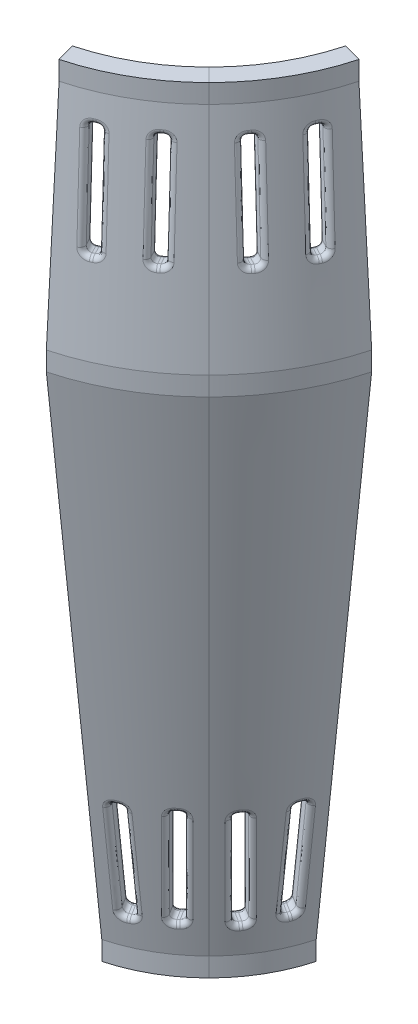
SolidWorks part; units mm, degrees
ref_plane "Front Plane" through (0, 0, 0) normal (0, 0, 1) x (1, 0, 0)
ref_plane "Top Plane" through (0, 0, 0) normal (0, 1, 0) x (1, 0, 0)
ref_plane "Right Plane" through (0, 0, 0) normal (1, 0, 0) x (0, 0, -1)
sketch "Sketch1" plane through (0, 0, 0) normal (0, 1, 0) x (1, 0, 0)
  line L0 (-28.2843, 28.2843) -> (-24.7487, 24.7487) construction
  line L1 (28.2843, 28.2843) -> (24.7487, 24.7487) construction
  line L2 (-24.7487, 24.7487) -> (0, 0) construction
  line L3 (24.7487, 24.7487) -> (0, 0) construction
  line L4 (0, 0) -> (0, 40) construction
  line L5 (-9.0587, -33.8074) -> (-10.3528, -38.637) construction
  line L6 (9.0587, -33.8074) -> (10.3528, -38.637)
  line L7 (0, 0) -> (9.0587, -33.8074) construction
  line L8 (0, 0) -> (-9.0587, -33.8074) construction
  line L9 (0, 0) -> (0, -40) construction
  line L10 (-24.7487, -24.7487) -> (-28.2843, -28.2843) construction
  line L11 (24.7487, -24.7487) -> (28.2843, -28.2843)
  line L12 (-24.7487, -24.7487) -> (0, 0) construction
  line L13 (0, 0) -> (24.7487, -24.7487) construction
  arc A0 (9.0587, -33.8074) -> (24.7487, -24.7487) centre (0, 0) ccw
  arc A1 (10.3528, -38.637) -> (28.2843, -28.2843) centre (0, 0) ccw
  arc A2 (-24.7487, -24.7487) -> (-9.0587, -33.8074) centre (0, 0) ccw construction
  arc A3 (-28.2843, -28.2843) -> (-10.3528, -38.637) centre (0, 0) ccw construction
  arc A4 (24.7487, 24.7487) -> (-24.7487, 24.7487) centre (0, 0) ccw construction
  arc A5 (28.2843, 28.2843) -> (-28.2843, 28.2843) centre (0, 0) ccw construction
  dimension "D1" = 70
  dimension "D2" = 5
  dimension "D3" = 45
  dimension "D4" = 45
  dimension "D5" = 15
  dimension "D6" = 15
  dimension "D7" = 30
  dimension "D8" = 30
ref_plane "Plane1" through (0, 152.4, 0) normal (0, 1, 0) x (1, 0, 0)
sketch "Sketch2" plane through (0, 152.4, 0) normal (0, 1, 0) x (1, 0, 0)
  line L0 (0, 0) -> (24.7487, -24.7487) construction
  line L1 (0, 0) -> (9.0587, -33.8074) construction
  line L2 (0, 0) -> (-9.0587, -33.8074) construction
  line L3 (-24.7487, -24.7487) -> (0, 0) construction
  line L4 (24.7487, 24.7487) -> (0, 0) construction
  line L5 (0, 0) -> (0, 40) construction
  line L6 (-24.7487, 24.7487) -> (0, 0) construction
  line L7 (0, 0) -> (24.7487, -24.7487) construction
  line L8 (0, 0) -> (9.0587, -33.8074) construction
  line L9 (0, 0) -> (-9.0587, -33.8074) construction
  line L10 (-24.7487, -24.7487) -> (0, 0) construction
  line L11 (24.7487, 24.7487) -> (0, 0) construction
  line L12 (0, 0) -> (0, 40) construction
  line L13 (-24.7487, 24.7487) -> (0, 0) construction
  line L14 (-42.9214, 42.9214) -> (-39.3858, 39.3858) construction
  line L15 (42.9214, 42.9214) -> (39.3858, 39.3858) construction
  line L16 (-39.3858, -39.3858) -> (-42.9214, -42.9214) construction
  line L17 (-14.4162, -53.8021) -> (-15.7103, -58.6317) construction
  line L18 (14.4162, -53.8021) -> (15.7103, -58.6317)
  line L19 (39.3858, -39.3858) -> (42.9214, -42.9214)
  arc A0 (-39.3858, -39.3858) -> (-14.4162, -53.8021) centre (0, 0) ccw construction
  arc A1 (-42.9214, -42.9214) -> (-15.7103, -58.6317) centre (0, 0) ccw construction
  arc A2 (39.3858, 39.3858) -> (-39.3858, 39.3858) centre (0, 0) ccw construction
  arc A3 (42.9214, 42.9214) -> (-42.9214, 42.9214) centre (0, 0) ccw construction
  arc A4 (14.4162, -53.8021) -> (39.3858, -39.3858) centre (0, 0) ccw
  arc A5 (15.7103, -58.6317) -> (42.9214, -42.9214) centre (0, 0) ccw
  dimension "D1" = 111.4
  dimension "D2" = 5
ref_plane "Plane2" through (0, 215.9, 0) normal (0, 1, 0) x (1, 0, 0)
sketch "Sketch3" plane through (0, 215.9, 0) normal (0, 1, 0) x (1, 0, 0)
  line L0 (-24.7487, -24.7487) -> (0, 0) construction
  line L1 (0, 0) -> (-9.0587, -33.8074) construction
  line L2 (0, 0) -> (9.0587, -33.8074) construction
  line L3 (0, 0) -> (24.7487, -24.7487) construction
  line L4 (24.7487, 24.7487) -> (0, 0) construction
  line L5 (0, 0) -> (0, 40) construction
  line L6 (-24.7487, 24.7487) -> (0, 0) construction
  line L7 (-24.7487, -24.7487) -> (0, 0) construction
  line L8 (0, 0) -> (-9.0587, -33.8074) construction
  line L9 (0, 0) -> (9.0587, -33.8074) construction
  line L10 (0, 0) -> (24.7487, -24.7487) construction
  line L11 (24.7487, 24.7487) -> (0, 0) construction
  line L12 (0, 0) -> (0, 40) construction
  line L13 (-24.7487, 24.7487) -> (0, 0) construction
  line L14 (-36.0271, 36.0271) -> (-39.5626, 39.5626) construction
  line L15 (39.5626, 39.5626) -> (36.0271, 36.0271) construction
  line L16 (-36.0271, -36.0271) -> (-39.5626, -39.5626) construction
  line L17 (-13.1868, -49.2139) -> (-14.4809, -54.0435) construction
  line L18 (13.1868, -49.2139) -> (14.4809, -54.0435)
  line L19 (36.0271, -36.0271) -> (39.5626, -39.5626)
  arc A0 (-36.0271, -36.0271) -> (-13.1868, -49.2139) centre (0, 0) ccw construction
  arc A1 (-39.5626, -39.5626) -> (-14.4809, -54.0435) centre (0, 0) ccw construction
  arc A2 (39.5626, 39.5626) -> (-39.5626, 39.5626) centre (0, 0) ccw construction
  arc A3 (36.0271, 36.0271) -> (-36.0271, 36.0271) centre (0, 0) ccw construction
  arc A4 (13.1868, -49.2139) -> (36.0271, -36.0271) centre (0, 0) ccw
  arc A5 (14.4809, -54.0435) -> (39.5626, -39.5626) centre (0, 0) ccw
  dimension "D1" = 101.9
  dimension "D2" = 5
extrude "Boss-Extrude1" add sketch "Sketch2" against normal blind 5
extrude "Boss-Extrude2" add sketch "Sketch1" along normal blind 5 separate body
loft "Loft4" add section face at (18.4306, 5, 31.9227) section face at (28.6042, 147.4, 49.544) connector at (10.3528, 5, 38.637) connector at (15.7103, 147.4, 58.6317)
extrude "Boss-Extrude3" add sketch "Sketch3" against normal blind 5 separate body
loft "Loft6" add section face at (28.6042, 152.4, 49.544) section face at (26.2697, 210.9, 45.5004) connector at (14.4162, 152.4, 53.8021) connector at (13.1868, 210.9, 49.2139)
ref_plane "Plane3" through (17.2198, -4.3931, 29.8256) normal (-0.496, 0.1265, -0.8591) x (-0.8681, -0.0476, 0.4942)
ref_plane "Plane4" through (27.85, 152.4, 48.2376) normal (-0.4984, -0.0809, -0.8632) x (-0.867, 0.0465, 0.4962)
sketch "Sketch10" plane through (27.85, 152.4, 48.2376) normal (-0.4984, -0.0809, -0.8632) x (-0.867, 0.0465, 0.4962)
  line L16 (-10.1939, 64.3626) -> (16.151, 63.1316) construction
  line L21 (16.151, 63.1316) -> (17.4255, 62.6808) construction
  line L22 (-11.5048, 64.0325) -> (-10.1939, 64.3626) construction
  line L23 (-4.9555, 51.4039) -> (-1.7839, 51.2557)
  line L24 (-4.9555, 51.4039) -> (-6.2892, 22.8601)
  line L25 (-6.2892, 22.8601) -> (-3.1176, 22.7119)
  line L26 (-1.7839, 51.2557) -> (-3.1176, 22.7119)
  line L27 (7.7411, 50.8107) -> (10.9126, 50.6625)
  line L28 (7.7411, 50.8107) -> (6.4074, 22.2668)
  line L29 (6.4074, 22.2668) -> (9.5789, 22.1186)
  line L30 (10.9126, 50.6625) -> (9.5789, 22.1186)
  line L31 (-1.7839, 51.2557) -> (7.7411, 50.8107) construction
  point P8 (2.9786, 51.0332)
  point P13 (2.9786, 63.7471)
  point P16 (11.1664, 25.8769)
  point P18 (-3.3697, 51.3298)
  dimension "D1" = 3.175
  dimension "D2" = 28.575
  dimension "D3" = 9.525
  dimension "D4" = 12.7
extrude "Cut-Extrude4" cut sketch "Sketch10" against normal through all both and the other way through all
sketch "Sketch11" plane through (17.2198, -4.3931, 29.8256) normal (-0.496, 0.1265, -0.8591) x (-0.8681, -0.0476, 0.4942)
  line L0 (-9.4971, 46.1269) -> (-7.0629, 17.6541)
  line L1 (-7.0629, 17.6541) -> (-3.8879, 17.6541)
  line L2 (-3.8879, 17.6541) -> (-6.3221, 46.1269)
  line L3 (-6.3221, 46.1269) -> (-9.4971, 46.1269)
  line L4 (1.8595, 46.2291) -> (2.1681, 17.6541)
  line L5 (2.1681, 17.6541) -> (5.3431, 17.6541)
  line L6 (5.3431, 17.6541) -> (5.0345, 46.2291)
  line L7 (5.0345, 46.2291) -> (1.8595, 46.2291)
  line L8 (-9.4918, 8.7919) -> (-21.7482, 152.1541) construction
  line L9 (8.6046, 9.6619) -> (7.051, 153.5387) construction
  ellipse E0 centre (-0.2382, 4.9541) end of major axis (-35.1978, 3.2733) minor radius 4.4287 (8.6046, 9.6619) -> (-9.4918, 8.7919) ccw construction
  dimension "D1" = 3.175
  dimension "D2" = 3.175
  dimension "D3" = 3.175
  dimension "D4" = 3.175
  dimension "D5" = 3.175
  dimension "D6" = 28.575
  dimension "D7" = 12.7
  dimension "D8" = 12.7
extrude "Cut-Extrude5" cut sketch "Sketch11" along normal through all and the other way through all
fillet "Fillet1" radius 1.27 48 edges at (31.7763, 174.8427, 43.5095) (34.2726, 175.2482, 47.8341) (30.6132, 203.3229, 41.4946) (33.1107, 203.7285, 45.8212) (13.9488, 13.0189, 33.3674) (16.4216, 12.3883, 37.6484) (17.5063, 40.6647, 41.6553) (15.0294, 41.2964, 37.367) (24.8956, 41.7358, 31.7416) (27.3711, 41.1041, 36.031) (24.4434, 12.8276, 33.0884) (21.9722, 13.4583, 28.8063) (17.74, 41.0332, 38.8815) (16.6452, 12.7594, 34.8571) (13.7, 12.6564, 36.0986) (14.7735, 40.9357, 40.086) (21.9039, 13.0475, 31.8675) (24.8416, 41.3213, 34.8275) (27.3896, 41.5257, 32.8982) (24.4732, 13.2464, 29.9749) (30.5581, 203.5376, 44.5795) (33.1382, 203.51, 42.6984) (19.5272, 203.311, 47.7259) (19.2932, 203.4958, 50.4891) (22.032, 203.7177, 52.0633) (22.2478, 203.5291, 49.2566) (20.6939, 174.8314, 49.7461) (23.4096, 175.0487, 51.2689) (23.197, 175.2378, 54.0806) (20.4636, 175.0168, 52.5162) (34.3048, 175.0305, 44.7191) (31.7177, 175.0568, 46.588)
sketch "Sketch9" plane through (17.2198, -4.3931, 29.8256) normal (-0.496, 0.1265, -0.8591) x (-0.8681, -0.0476, 0.4942)
  line L0 (-21.7482, 152.1541) -> (-8.1415, 169.3376) construction
  line L1 (-8.1415, 169.3376) -> (7.051, 153.5387) construction
  line L2 (-21.7482, 152.1541) -> (7.051, 153.5387) construction
  line L7 (-2.9281, 171.09) -> (9.7719, 171.7006)
  line L8 (-2.7841, 168.0934) -> (9.9159, 168.704)
  line L29 (9.9159, 168.704) -> (9.7719, 171.7006)
  line L31 (-13.3549, 167.5852) -> (-26.0549, 166.9746)
  line L32 (-26.0549, 166.9746) -> (-26.1989, 169.9711)
  line L33 (-26.1989, 169.9711) -> (-13.4989, 170.5817)
  line L35 (-26.1269, 168.4729) -> (9.8439, 170.2023) construction
  line L36 (-9.4918, 8.7919) -> (8.6046, 9.6619) construction
  line L38 (-7.3486, 152.8464) -> (-0.4436, 9.2269) construction
  line L40 (-11.5231, 129.4852) -> (-24.2231, 128.8746)
  line L41 (-24.2231, 128.8746) -> (-24.3671, 131.8711)
  line L42 (-24.3671, 131.8711) -> (-11.6671, 132.4817)
  line L43 (-1.0964, 132.99) -> (11.6036, 133.6006)
  line L44 (11.7477, 130.604) -> (11.6036, 133.6006)
  line L45 (-0.9523, 129.9934) -> (11.7477, 130.604)
  line L46 (-9.6913, 91.3852) -> (-22.3913, 90.7746)
  line L47 (-22.3913, 90.7746) -> (-22.5354, 93.7711)
  line L48 (-22.5354, 93.7711) -> (-9.8354, 94.3817)
  line L49 (0.7354, 94.89) -> (13.4354, 95.5006)
  line L50 (13.5795, 92.504) -> (13.4354, 95.5006)
  line L51 (0.8795, 91.8934) -> (13.5795, 92.504)
  line L52 (-7.8595, 53.2852) -> (-20.5595, 52.6746)
  line L53 (-20.5595, 52.6746) -> (-20.7036, 55.6711)
  line L54 (-20.7036, 55.6711) -> (-8.0036, 56.2817)
  line L55 (2.5672, 56.79) -> (15.2672, 57.4006)
  line L56 (15.4113, 54.404) -> (15.2672, 57.4006)
  line L57 (2.7113, 53.7934) -> (15.4113, 54.404)
  line L58 (-23.7555, 219.5043) -> (2.5877, 220.7709) construction
  arc A10 (-13.3549, 167.5852) -> (-2.7841, 168.0934) centre (-8.1415, 169.3376) ccw
  arc A11 (-2.9281, 171.09) -> (-13.4989, 170.5817) centre (-8.1415, 169.3376) ccw
  arc A12 (-1.0964, 132.99) -> (-11.6671, 132.4817) centre (-6.3097, 131.2376) ccw
  arc A13 (-11.5231, 129.4852) -> (-0.9523, 129.9934) centre (-6.3097, 131.2376) ccw
  arc A14 (0.7354, 94.89) -> (-9.8354, 94.3817) centre (-4.4779, 93.1376) ccw
  arc A15 (-9.6913, 91.3852) -> (0.8795, 91.8934) centre (-4.4779, 93.1376) ccw
  arc A16 (2.5672, 56.79) -> (-8.0036, 56.2817) centre (-2.6461, 55.0376) ccw
  arc A17 (-7.8595, 53.2852) -> (2.7113, 53.7934) centre (-2.6461, 55.0376) ccw
  point P46 (0, 0)
  point P47 (0, 0)
  point P48 (-10.5839, 220.1376)
  dimension "D1" = 11
  dimension "D2" = 50.8
  dimension "D3" = 3
  dimension "D4" = 12.7
  dimension "D6" = 38.1
  dimension "D5" = 4
extrude "Cut-Extrude3" cut sketch "Sketch9" against normal blind 1 and the other way through all
sketch "Sketch12" plane through (17.2198, -4.3931, 29.8256) normal (-0.496, 0.1265, -0.8591) x (-0.8683, -0.0723, 0.4907)
  line L18 (-27.422, 128.232) -> (-14.7411, 129.1584)
  line L19 (-27.6406, 131.2241) -> (-27.422, 128.232)
  line L20 (-14.9597, 132.1504) -> (-27.6406, 131.2241)
  line L21 (8.2761, 133.8479) -> (-4.4048, 132.9215)
  line L22 (8.4946, 130.8559) -> (8.2761, 133.8479)
  line L23 (-4.1862, 129.9295) -> (8.4946, 130.8559)
  line L24 (-27.422, 128.232) -> (-14.7411, 129.1584)
  line L25 (-27.6406, 131.2241) -> (-27.422, 128.232)
  line L26 (-14.9597, 132.1504) -> (-27.6406, 131.2241)
  line L27 (8.2761, 133.8479) -> (-4.4048, 132.9215)
  line L28 (8.4946, 130.8559) -> (8.2761, 133.8479)
  line L29 (-4.1862, 129.9295) -> (8.4946, 130.8559)
  arc A6 (-4.4048, 132.9215) -> (-14.9597, 132.1504) centre (-9.573, 131.04) ccw
  arc A7 (-14.7411, 129.1584) -> (-4.1862, 129.9295) centre (-9.573, 131.04) ccw
  arc A8 (-4.4048, 132.9215) -> (-14.9597, 132.1504) centre (-9.573, 131.04) ccw
  arc A9 (-14.7411, 129.1584) -> (-4.1862, 129.9295) centre (-9.573, 131.04) ccw
  dimension "D2" = 0
extrude "Cut-Extrude6" cut sketch "Sketch12" against normal blind 3
sketch "Sketch13" plane through (17.2198, -4.3931, 29.8256) normal (-0.496, 0.1265, -0.8591) x (-0.8681, -0.0476, 0.4942)
  line L30 (-20.5595, 52.6746) -> (-7.8595, 53.2852)
  line L31 (-20.7036, 55.6711) -> (-20.5595, 52.6746)
  line L32 (-8.0036, 56.2817) -> (-20.7036, 55.6711)
  line L33 (15.2672, 57.4006) -> (2.5672, 56.79)
  line L34 (15.4113, 54.404) -> (15.2672, 57.4006)
  line L35 (2.7113, 53.7934) -> (15.4113, 54.404)
  line L36 (-20.5595, 52.6746) -> (-7.8595, 53.2852)
  line L37 (-20.7036, 55.6711) -> (-20.5595, 52.6746)
  line L38 (-8.0036, 56.2817) -> (-20.7036, 55.6711)
  line L39 (15.2672, 57.4006) -> (2.5672, 56.79)
  line L40 (15.4113, 54.404) -> (15.2672, 57.4006)
  line L41 (2.7113, 53.7934) -> (15.4113, 54.404)
  line L42 (-22.3913, 90.7746) -> (-9.6913, 91.3852)
  line L43 (-22.5354, 93.7711) -> (-22.3913, 90.7746)
  line L44 (-9.8354, 94.3817) -> (-22.5354, 93.7711)
  line L45 (13.4354, 95.5006) -> (0.7354, 94.89)
  line L46 (13.5795, 92.504) -> (13.4354, 95.5006)
  line L47 (0.8795, 91.8934) -> (13.5795, 92.504)
  line L48 (-22.3913, 90.7746) -> (-9.6913, 91.3852)
  line L49 (-22.5354, 93.7711) -> (-22.3913, 90.7746)
  line L50 (-9.8354, 94.3817) -> (-22.5354, 93.7711)
  line L51 (13.4354, 95.5006) -> (0.7354, 94.89)
  line L52 (13.5795, 92.504) -> (13.4354, 95.5006)
  line L53 (0.8795, 91.8934) -> (13.5795, 92.504)
  arc A10 (2.5672, 56.79) -> (-8.0036, 56.2817) centre (-2.6461, 55.0376) ccw
  arc A11 (-7.8595, 53.2852) -> (2.7113, 53.7934) centre (-2.6461, 55.0376) ccw
  arc A12 (2.5672, 56.79) -> (-8.0036, 56.2817) centre (-2.6461, 55.0376) ccw
  arc A13 (-7.8595, 53.2852) -> (2.7113, 53.7934) centre (-2.6461, 55.0376) ccw
  arc A14 (0.7354, 94.89) -> (-9.8354, 94.3817) centre (-4.4779, 93.1376) ccw
  arc A15 (-9.6913, 91.3852) -> (0.8795, 91.8934) centre (-4.4779, 93.1376) ccw
  arc A16 (0.7354, 94.89) -> (-9.8354, 94.3817) centre (-4.4779, 93.1376) ccw
  arc A17 (-9.6913, 91.3852) -> (0.8795, 91.8934) centre (-4.4779, 93.1376) ccw
  dimension "D3" = 0
  dimension "D4" = 0
extrude "Cut-Extrude7" cut sketch "Sketch13" against normal blind 2.5
fillet "Fillet2" radius 0.508 24 edges at (30.5865, 86.6154, 35.5064) (30.8497, 89.5851, 35.8495) (24.1445, 93.4352, 41.3181) (23.9005, 82.6249, 39.6355) (15.6217, 89.5851, 44.6413) (15.4562, 86.6154, 44.2419) (13.3509, 48.8578, 39.1622) (13.5166, 51.8274, 39.5618) (21.3205, 55.6856, 36.6125) (27.5032, 51.8274, 31.4866) (27.24, 48.8578, 31.1433) (21.1395, 44.8689, 34.8912) (17.5603, 124.3734, 49.3198) (25.9995, 120.3083, 44.7584) (33.932, 124.3734, 39.8676) (34.1951, 127.343, 40.2105) (26.6051, 131.1933, 46.236) (17.7258, 127.343, 49.7191) (35.3193, 165.5622, 41.6788) (35.4705, 162.5065, 41.8759) (18.5304, 162.5065, 51.6563) (27.9526, 158.3334, 47.6204) (18.4353, 165.5622, 51.4268) (27.1093, 169.5235, 47.0598)
pattern_circular "CirPattern8" count 2 over 330 about axis through (0, 215.9, 0) along (0, -1, 0) of bodies 128 120
